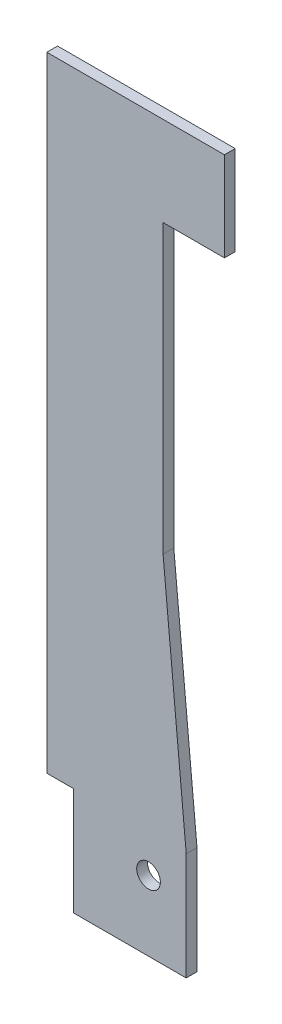
SolidWorks part; units mm, degrees
ref_plane "前视基准面" through (0, 0, 0) normal (0, 0, 1) x (1, 0, 0)
ref_plane "上视基准面" through (0, 0, 0) normal (0, 1, 0) x (1, 0, 0)
ref_plane "右视基准面" through (0, 0, 0) normal (1, 0, 0) x (0, 0, -1)
sketch "草图1" plane through (0, 0, 0) normal (0, 0, 1) x (1, 0, 0)
  line L0 (5.4112, -12.7018) -> (5.4112, -40.2018) construction
  line L1 (5.4112, -12.7018) -> (-5.5888, -12.7018) construction
  line L2 (5.4112, -12.7018) -> (5.4112, 12.2982) construction
  line L4 (-5.5888, -12.7018) -> (-5.5888, 13.1187)
  line L5 (0, 0) -> (-5.5888, 13.1187) construction
  line L6 (5.4112, 12.2982) -> (-5.5888, -12.7018) construction
  line L8 (-5.5888, -12.7018) -> (-5.5888, -40.2018)
  line L12 (-5.5888, 13.1187) -> (-5.5888, 17.7982)
  line L13 (-5.5888, 17.7982) -> (13.9112, 17.7982)
  line L14 (13.9112, 12.5) -> (13.9112, 17.7982)
  line L15 (-5.5888, -40.2018) -> (5.4112, -40.2018)
  line L23 (10.3611, -40.2018) -> (8.2112, -17.1977)
  line L24 (5.4112, -40.2018) -> (-0.0888, -40.2018)
  line L25 (5.4112, -40.2018) -> (5.4112, -50.2018) construction
  line L26 (5.4112, -50.2018) -> (-0.0888, -50.2018)
  line L27 (-0.0888, -40.2018) -> (-0.0888, -50.2018)
  line L28 (5.4112, -40.2018) -> (10.3611, -40.2018)
  line L29 (5.4112, -40.2018) -> (5.4112, -50.2018) construction
  line L30 (5.4112, -50.2018) -> (10.3611, -50.2018)
  line L31 (10.3611, -40.2018) -> (10.3611, -50.2018)
  line L32 (5.4112, -12.7018) -> (0, 0) construction
  line L33 (8.2112, 9.5) -> (8.2112, -17.1977)
  line L34 (13.9112, 12.5) -> (13.9112, 9.5)
  line L35 (13.9112, 9.5) -> (8.2112, 9.5)
  circle A1 centre (6.8611, -43.7018) radius 1.1
  point P0 (0, 0)
  point P19 (9.6052, 12.5)
  dimension "D7" = 27.5
  dimension "D9" = 3.5
  dimension "D8" = 2.2
  dimension "D1" = 25
  dimension "D2" = 11
  dimension "D3" = 30.5
  dimension "D4" = 19.5
  dimension "D5" = 10
  dimension "D6" = 5.5
  dimension "D10" = 3.5
  dimension "D11" = 4.9499
  dimension "D12" = 2.8
  dimension "D13" = 3
extrude "凸台-拉伸2" add sketch "草图1" along normal blind 1
extrude "凸台-拉伸3" add sketch "草图1<5>" along normal blind 1 contours L15 L27 L26 L25 A1 region at (5.071, -45.2585, 0)
sketch "草图1<5>" plane through (0, 0, 0) normal (0, 0, 1) x (1, 0, 0) same geometry as "草图1"
sketch "草图3" plane through (0, 0, 1) normal (0, 0, 1) x (1, 0, 0)
  line L0 (-5.5888, -40.2018) -> (-0.0888, -40.2018) construction
  line L1 (-5.5888, 17.7982) -> (-2.5888, 17.7982)
  line L2 (-5.5888, 17.7982) -> (-5.5888, -40.2018)
  line L3 (-5.5888, -40.2018) -> (-2.5888, -40.2018)
  line L4 (-2.5888, 17.7982) -> (-2.5888, -40.2018)
  dimension "D1" = 3
extrude "切除-拉伸1" cut sketch "草图3" against normal blind 10
